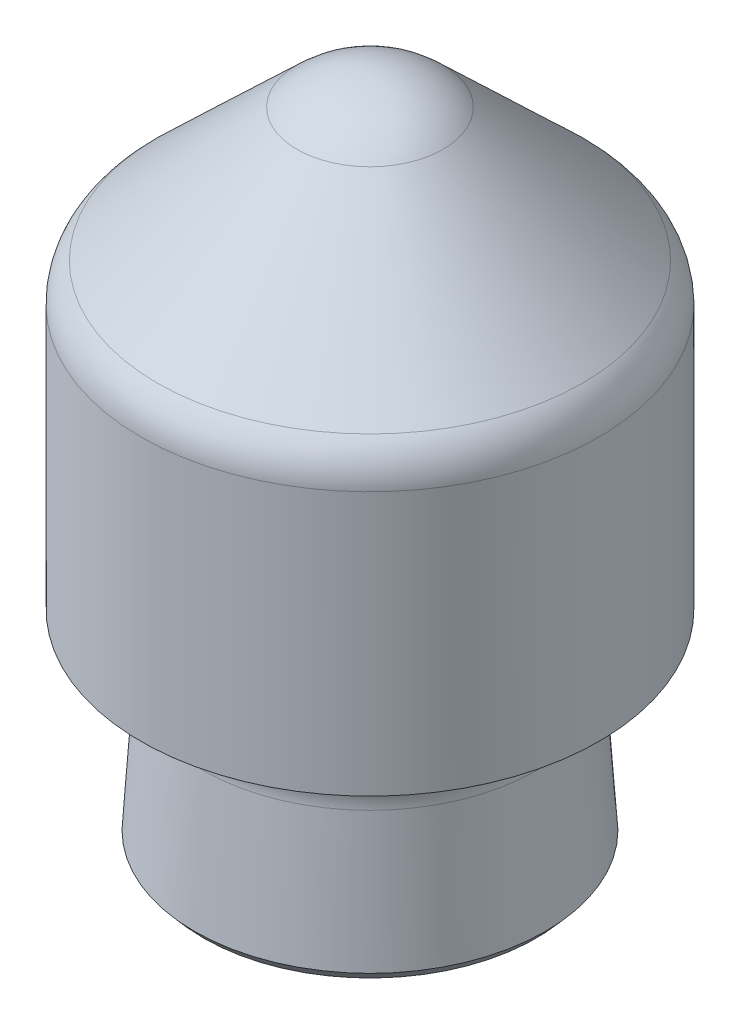
SolidWorks part; units mm, degrees
material "6061-T6 (SS)"
ref_plane "Front Plane" through (0, 0, 0) normal (0, 0, 1) x (1, 0, 0)
ref_plane "Top Plane" through (0, 0, 0) normal (0, 1, 0) x (1, 0, 0)
ref_plane "Right Plane" through (0, 0, 0) normal (1, 0, 0) x (0, 0, -1)
sketch "Sketch1" plane through (0, 0, 0) normal (0, 0, 1) x (1, 0, 0)
  line L0 (0, 25.4) -> (0, 41.3512) construction
  line L1 (3.6957, 25.4) -> (-3.6957, 25.4) construction
  line L2 (4.7085, 14.7066) -> (-4.7085, 14.7066) construction
  line L3 (0, 25.4) -> (-4.2164, 25.4)
  line L4 (-3.899, 30.2387) -> (-4.2164, 25.4)
  line L5 (0, 25.4) -> (0, 41.3512)
  line L6 (-3.899, 30.2387) -> (-5.4864, 30.2387)
  line L7 (-5.4864, 30.2387) -> (-5.4864, 37.0967)
  line L8 (-1.7509, 40.6513) -> (-5.4864, 37.0967)
  arc A0 (-1.7509, 40.6513) -> (0, 41.3512) centre (0, 38.8112) cw
  dimension "D6" = 2.54
  dimension "D1" = 26.6446
  dimension "D2" = 3.899
  dimension "D3" = 10.9728
  dimension "D4" = 4.2545
  dimension "D5" = 11.1125
  dimension "D7" = 1.27
revolve "Revolve1" add sketch "Sketch1" angle 360 about L0
fillet "Fillet1" radius 1.27 1 edges at (0, 37.0967, -5.4864)
fillet "Fillet2" radius 1.27 1 edges at (0, 30.2387, -3.899)
chamfer "Chamfer1" distance 0.254 angle 45 1 edges at (0, 25.4, -4.2164) first distance on face at (0, 28.8856, -3.9878)
